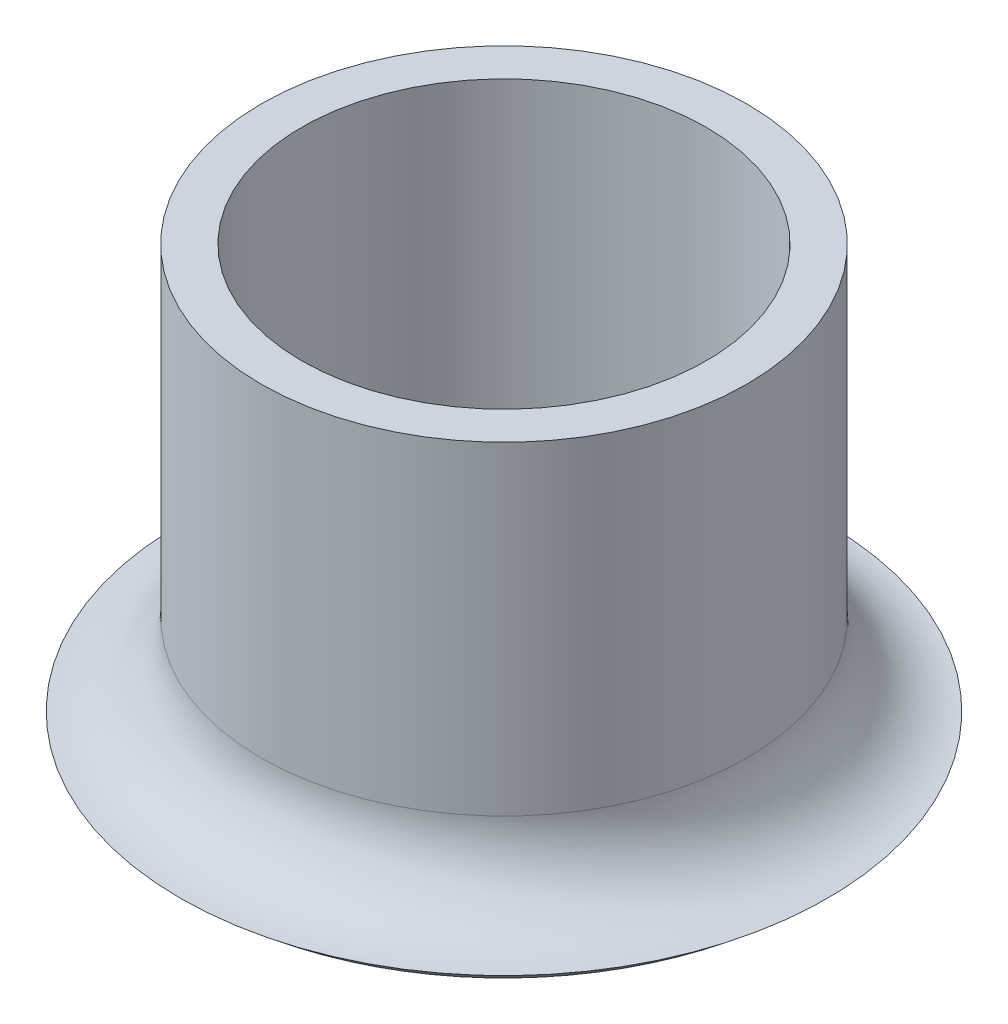
SolidWorks part; units mm, degrees
ref_plane "Front Plane" through (0, 0, 0) normal (0, 0, 1) x (1, 0, 0)
ref_plane "Top Plane" through (0, 0, 0) normal (0, 1, 0) x (1, 0, 0)
ref_plane "Right Plane" through (0, 0, 0) normal (1, 0, 0) x (0, 0, -1)
sketch "Sketch1" plane through (0, 0, 0) normal (0, 1, 0) x (1, 0, 0)
  circle A0 centre (0, 0) radius 3
  dimension "D1" = 6
extrude "Boss-Extrude1" add sketch "Sketch1" along normal blind 5
sketch "Sketch2" plane through (0, 5, 0) normal (0, 1, 0) x (1, 0, 0)
  circle A0 centre (0, 0) radius 2.5
extrude "Cut-Extrude1" cut sketch "Sketch2" against normal blind 4 contours A0
sketch "Sketch3" plane through (0, 0, 0) normal (0, -1, 0) x (1, 0, 0)
  circle A0 centre (0, 0) radius 4
  dimension "D1" = 8
extrude "Boss-Extrude3" add sketch "Sketch3" along normal blind 1
fillet "Fillet2" radius 1 1 edges at (0, 0, 3)
fillet "Fillet3" radius 4 1 edges at (0, -1, -4)
